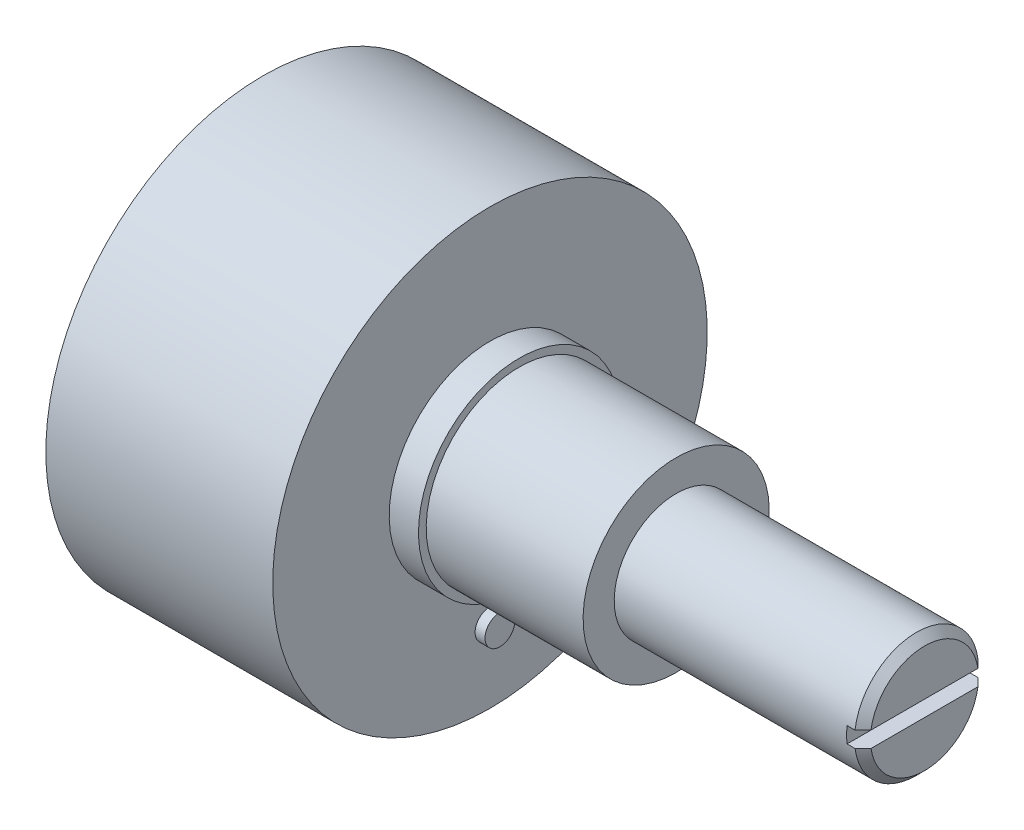
SolidWorks part; units mm, degrees
material "Plain Carbon Steel"
ref_plane "Front Plane" through (0, 0, 0) normal (0, 0, 1) x (1, 0, 0)
ref_plane "Top Plane" through (0, 0, 0) normal (0, 1, 0) x (1, 0, 0)
ref_plane "Right Plane" through (0, 0, 0) normal (1, 0, 0) x (0, 0, -1)
ref_axis "X Axis" through (-88.99, 0, 0) along (1, 0, 0)
ref_axis "Y Axis" through (0, 55, 0) along (0, -1, 0)
ref_axis "Z Axis" through (0, 0, -88.99) along (0, 0, 1)
sketch "Sketch2" plane through (0, 0, 0) normal (0, 0, 1) x (1, 0, 0)
  line L0 (22.225, 0) -> (203.1823, 0) construction
  line L1 (0, 0) -> (22.225, 0)
  line L3 (0, 5.1562) -> (1.4986, 5.1562)
  line L4 (1.4986, 4.7625) -> (1.4986, 5.1562)
  line L5 (0, 0) -> (-11.6078, 0)
  line L6 (0, 5.1562) -> (0, 11.1125)
  line L7 (0, 11.1125) -> (-11.6078, 11.1125)
  line L8 (-11.6078, 0) -> (-11.6078, 11.1125)
  line L11 (1.4986, 4.7625) -> (9.525, 4.7625)
  line L12 (9.525, 3.1712) -> (9.525, 4.7625)
  line L15 (9.525, 3.1712) -> (22.225, 3.1712)
  line L16 (22.225, 0) -> (22.225, 3.1712)
  line L17 (0, 5.1562) -> (0, 0) construction
  line L18 (1.4986, 4.7625) -> (1.4986, 0) construction
  line L19 (9.525, 3.1712) -> (9.525, 0) construction
  point P3 (22.225, 1.5856)
  dimension "D1" = 1.4986
  dimension "D2" = 22.225
  dimension "D3" = 11.6078
  dimension "D4" = 6.3424
  dimension "D5" = 9.525
  dimension "D6" = 9.525
  dimension "D7" = 10.3124
  dimension "D8" = 22.225
revolve "Revolve1" add sketch "Sketch2" angle 360 about L0
sketch "Sketch3" plane through (0, 0, 0) normal (1, 0, 0) x (0, 0, -1)
  circle A0 centre (0, -7.366) radius 0.762
  dimension "D1" = 1.524
  dimension "D2" = 7.366
extrude "Boss-Extrude1" add sketch "Sketch3" along normal mid plane 1.016
sketch "Sketch4" plane through (0, 0, 0) normal (0, 0, 1) x (1, 0, 0)
  line L0 (22.225, -3.1712) -> (22.225, 3.1712) construction
  line L1 (22.225, 0.4064) -> (21.4122, 0.4064)
  line L2 (22.225, 0.4064) -> (22.225, -0.4064)
  line L3 (22.225, -0.4064) -> (21.4122, -0.4064)
  line L4 (21.4122, 0.4064) -> (21.4122, -0.4064)
  point P4 (22.225, 0)
  dimension "D1" = 0.8128
  dimension "D2" = 0.8128
extrude "Cut-Extrude1" cut sketch "Sketch4" against normal through all both and the other way through all
chamfer "Chamfer1" distance 0.4064 angle 45 2 edges at (22.225, -3.1712, 0) (22.225, 3.1712, 0)
